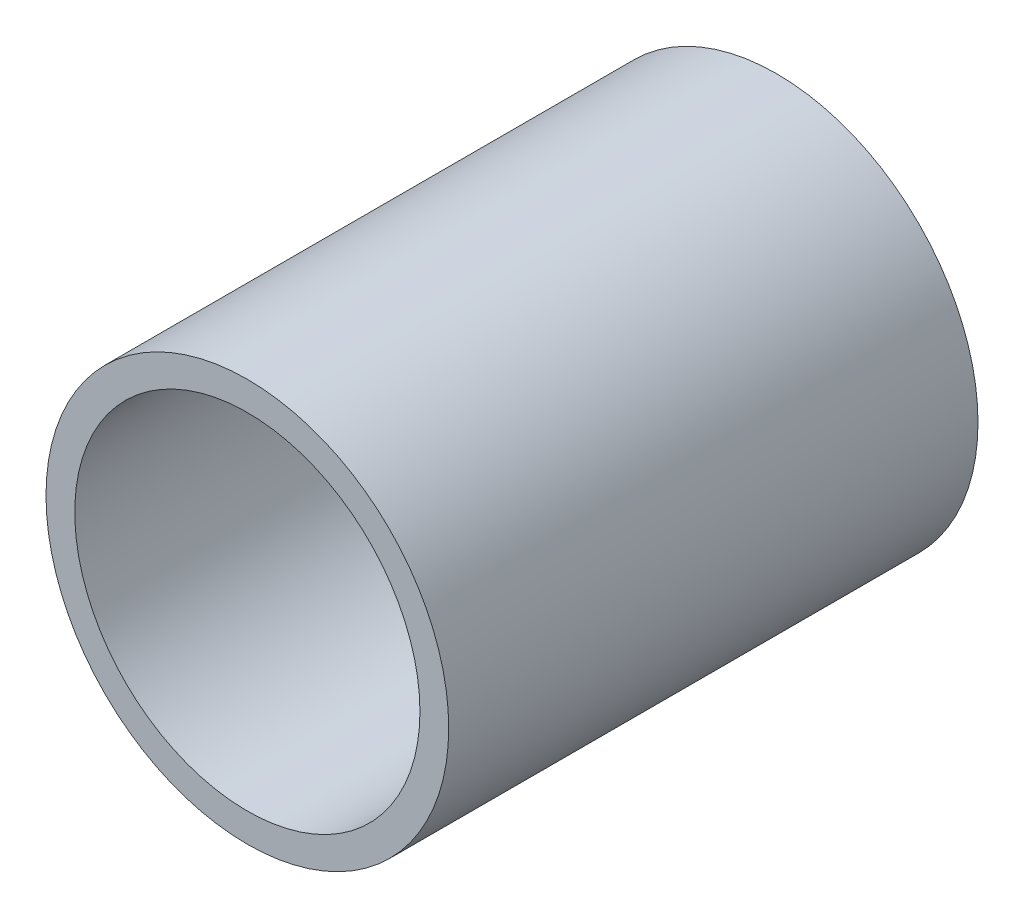
SolidWorks part; units mm, degrees
ref_plane "Ebene vorne" through (0, 0, 0) normal (1, 0, 0) x (0, 1, 0)
ref_plane "Ebene oben" through (0, 0, 0) normal (0, 0, 1) x (0, 1, 0)
ref_plane "Ebene rechts" through (0, 0, 0) normal (0, 1, 0) x (-1, 0, 0)
sketch "Skizze1" plane through (0, 0, 0) normal (0, 0, 1) x (0, 1, 0)
  circle A0 centre (0, 0) radius 60
  circle A1 centre (0, 0) radius 70
  dimension "D1" = 120
  dimension "D2" = 140
extrude "Aufsatz-Linear austragen1" add sketch "Skizze1" against normal blind 184
sketch "Skizze3" plane through (0, 0, 0) normal (0, 0, 1) x (0, 1, 0)
  line L0 (-70, 0) -> (70, 0) construction
  line L1 (0, -70) -> (0, 70) construction
  circle A0 centre (0, 0) radius 70 construction
  circle A1 centre (0, 0) radius 65 construction
  circle A2 centre (-65, 0) radius 2
  circle A3 centre (0, 65) radius 2
  circle A4 centre (65, 0) radius 2
  circle A5 centre (0, -65) radius 2
